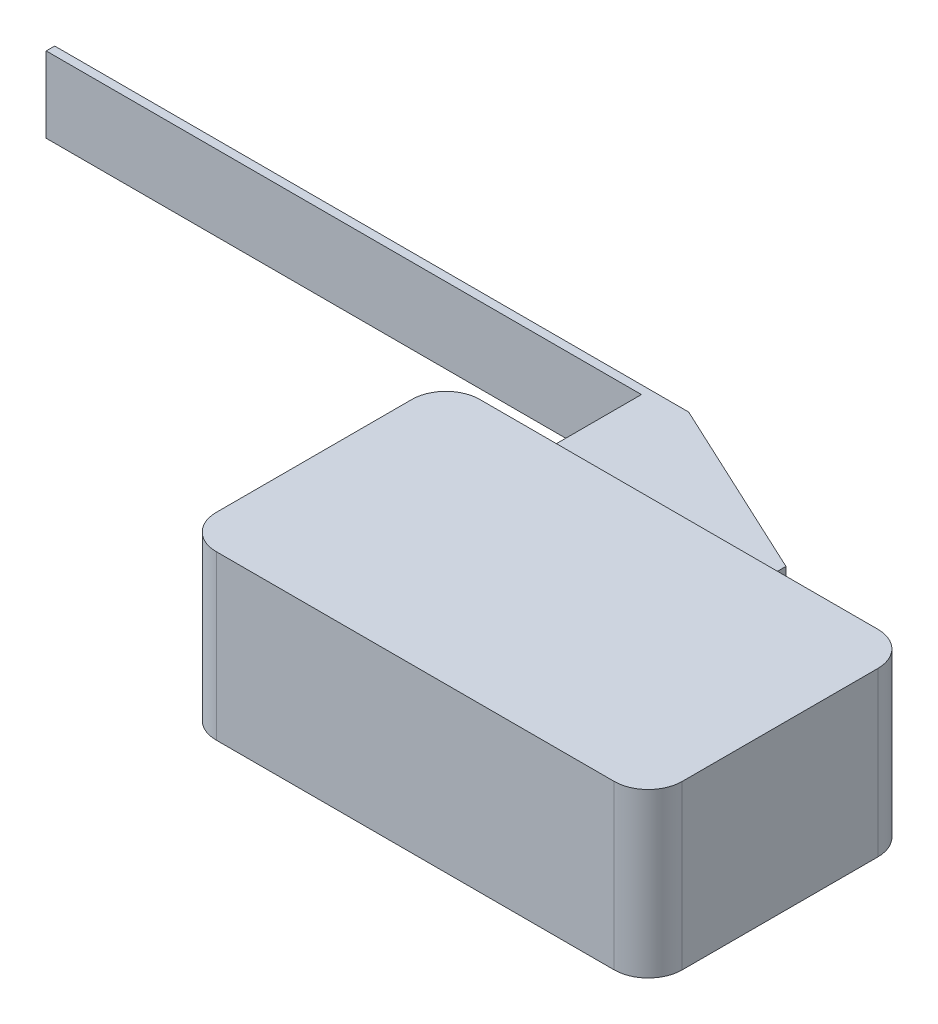
SolidWorks part; units mm, degrees
ref_plane "Front Plane" through (0, 0, 0) normal (0, 0, 1) x (1, 0, 0)
ref_plane "Top Plane" through (0, 0, 0) normal (0, 1, 0) x (1, 0, 0)
ref_plane "Right Plane" through (0, 0, 0) normal (1, 0, 0) x (0, 0, -1)
sketch "Sketch1" plane through (0, 0, 0) normal (0, 1, 0) x (1, 0, 0)
  line L1 (0, 0) -> (27.4, 0)
  line L2 (0, 0) -> (0, 15.5)
  line L3 (0, 15.5) -> (27.4, 15.5)
  line L4 (27.4, 0) -> (27.4, 15.5)
  dimension "D1" = 15.5
  dimension "D2" = 27.4
extrude "Boss-Extrude1" add sketch "Sketch1" along normal blind 9.6
fillet "Fillet1" radius 2 4 edges at (0, 4.8, -15.5) (27.4, 4.8, -15.5) (0, 4.8, 0) (27.4, 4.8, 0)
sketch "Sketch2" plane through (0, 0, -15.5) normal (0, 0, -1) x (-1, 0, 0)
  line L0 (-25.4, 9.6) -> (-2, 9.6) construction
  line L1 (-4, 2.65) -> (-17, 2.65)
  line L2 (-4, 2.65) -> (-4, 7.1)
  line L3 (-4, 7.1) -> (-17, 7.1)
  line L4 (-17, 2.65) -> (-17, 7.1)
  line L6 (0, 9.6) -> (0, 0) construction
  point P8 (42.8308, 13.1737)
  dimension "D1" = 4.45
  dimension "D2" = 2.5
  dimension "D3" = 13
  dimension "D4" = 4
extrude "Boss-Extrude2" add sketch "Sketch2" along normal blind 8
sketch "Sketch3" plane through (4, 0, 0) normal (-1, 0, 0) x (0, 0, 1)
  line L0 (-23.5, 7.1) -> (-15.5, 7.1) construction
  line L1 (-23.5, 2.65) -> (-23, 2.65)
  line L2 (-23.5, 2.65) -> (-23.5, 7.1)
  line L3 (-23.5, 7.1) -> (-23, 7.1)
  line L4 (-23, 2.65) -> (-23, 7.1)
  dimension "D1" = 0.5
extrude "Boss-Extrude3" add sketch "Sketch3" along normal blind 35
chamfer "Chamfer1" distance 5 angle 65 1 edges at (17, 4.875, -23.5) first distance on face at (17, 4.875, -19.5)
